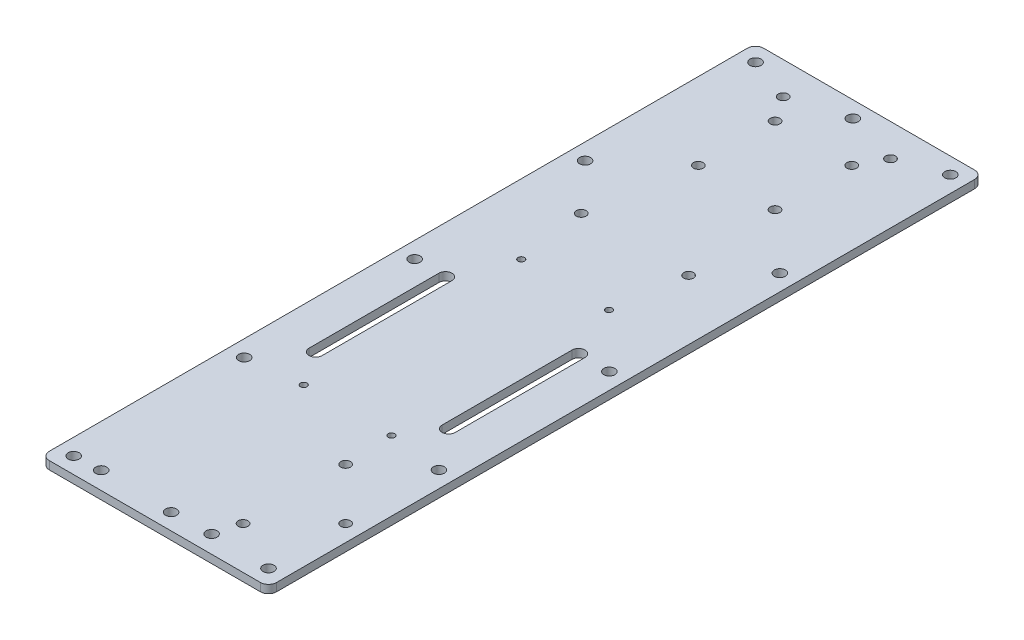
SolidWorks part; units mm, degrees
ref_plane "Front Plane" through (0, 0, 0) normal (0, 0, 1) x (1, 0, 0)
ref_plane "Top Plane" through (0, 0, 0) normal (0, 1, 0) x (1, 0, 0)
ref_plane "Right Plane" through (0, 0, 0) normal (1, 0, 0) x (0, 0, -1)
sketch "Sketch2" plane through (0, 0, 0) normal (0, 1, 0) x (1, 0, 0)
  line L0 (-44.45, 0) -> (44.45, 0) construction
  line L1 (-41.275, 139.7) -> (41.275, 139.7)
  line L2 (-44.45, 136.525) -> (-44.45, -136.525)
  line L3 (-41.275, -139.7) -> (41.275, -139.7)
  line L4 (44.45, 136.525) -> (44.45, -136.525)
  line L5 (0, 139.7) -> (0, -139.7) construction
  arc A0 (-44.45, -136.525) -> (-41.275, -139.7) centre (-41.275, -136.525) ccw
  arc A1 (41.275, -139.7) -> (44.45, -136.525) centre (41.275, -136.525) ccw
  arc A2 (41.275, 139.7) -> (44.45, 136.525) centre (41.275, 136.525) cw
  arc A3 (-41.275, 139.7) -> (-44.45, 136.525) centre (-41.275, 136.525) ccw
  point P8 (0, 0)
  point P13 (-44.45, -139.7)
  point P16 (44.45, -139.7)
  point P21 (-44.45, 139.7)
  dimension "D3" = 3.175
  dimension "D1" = 279.4
  dimension "D2" = 88.9
extrude "Plate Thickness" add sketch "Sketch2" along normal blind 3.175 contours L2 A0 L3 A1 L4 A2 L1 A3
sketch "Sketch3" plane through (0, 3.175, 0) normal (0, 1, 0) x (1, 0, 0)
  line L0 (-44.45, 136.525) -> (-44.45, -136.525) construction
  line L1 (-41.275, 139.7) -> (41.275, 139.7) construction
  line L4 (0, 139.7) -> (0, -139.7) construction
  line L5 (-41.275, -139.7) -> (41.275, -139.7) construction
  circle A0 centre (-38.1, 133.35) radius 2.159
  circle A1 centre (-38.1, 66.675) radius 2.159
  circle A2 centre (-38.1, -66.675) radius 2.159
  circle A3 centre (-38.1, -133.35) radius 2.159
  circle A4 centre (38.1, -133.35) radius 2.159
  circle A5 centre (38.1, -66.675) radius 2.159
  circle A6 centre (38.1, 66.675) radius 2.159
  circle A7 centre (38.1, 133.35) radius 2.159
  circle A8 centre (0, 133.35) radius 2.159
  circle A9 centre (0, -133.35) radius 2.159
  circle A10 centre (-38.1, 0) radius 2.159
  circle A11 centre (38.1, 0) radius 2.159
  dimension "D1" = 4.318
  dimension "D4" = 4.318
  dimension "D2" = 6.35
  dimension "D3" = 6.35
  dimension "D5" = 66.675
  dimension "D6" = 6.35
  dimension "D7" = 66.675
extrude "Mounting holes" cut sketch "Sketch3" against normal through all
sketch "Sketch4" plane through (0, 3.175, 0) normal (0, 1, 0) x (1, 0, 0)
  line L0 (-21.0058, 48.0812) -> (21.0058, 48.0812) construction
  line L1 (0, 0) -> (0, 139.7) construction
  line L4 (-41.275, 139.7) -> (41.275, 139.7) construction
  circle A0 centre (-21.0058, 127.0752) radius 1.905
  circle A1 centre (-21.0058, 48.0812) radius 1.905
  circle A2 centre (21.0058, 48.0812) radius 1.905
  circle A3 centre (21.0058, 127.0752) radius 1.905
  point P13 (0, 48.0812)
  point P17 (0, 69.85)
  point P18 (0, 69.85)
  dimension "D1" = 3.81
  dimension "D2" = 78.994
  dimension "D3" = 42.0116
extrude "Jetson Holes (w/ mount)" cut sketch "Sketch4" against normal through all
sketch "Sketch5" plane through (0, 3.175, 0) normal (0, 1, 0) x (1, 0, 0)
  circle A1 centre (-14.3419, 117.2351) radius 1.905
  circle A3 centre (15.6555, 117.2351) radius 1.905
  circle A4 centre (15.6555, 87.2377) radius 1.905
  circle A5 centre (-14.3419, 87.2377) radius 1.905
  dimension "D1" = 3.81
  dimension "D2" = 29.9974
  dimension "D3" = 29.9974
extrude "PDB holes" cut sketch "Sketch5" against normal through all
sketch "Sketch6" plane through (0, 3.175, 0) normal (0, 1, 0) x (1, 0, 0)
  circle A6 centre (38.0032, -103.0828) radius 1.905
  circle A7 centre (17.9372, -83.0168) radius 1.905
  circle A8 centre (17.9372, -123.1488) radius 1.905
  dimension "D5" = 3.81
  dimension "D6" = 40.132
  dimension "D7" = 20.066
  dimension "D8" = 20.066
extrude "Lidar Holes" cut sketch "Sketch6" against normal through all
sketch "Sketch7" plane through (0, 3.175, 0) normal (0, 1, 0) x (1, 0, 0)
  line L0 (0, 139.7) -> (0, -139.7) construction
  line L1 (-41.275, 139.7) -> (41.275, 139.7) construction
  line L2 (-41.275, -139.7) -> (41.275, -139.7) construction
  line L3 (17.145, 20.7699) -> (-17.145, 20.7699) construction
  circle A0 centre (-17.145, 20.7699) radius 1.27
  circle A1 centre (-17.145, -64.3201) radius 1.27
  circle A2 centre (17.145, -64.3201) radius 1.27
  circle A3 centre (17.145, 20.7699) radius 1.27
  point P14 (0, 20.7699)
  dimension "D1" = 2.54
  dimension "D2" = 85.09
  dimension "D3" = 34.29
extrude "PixHawk Holes" cut sketch "Sketch7" against normal through all
sketch "Sketch8" plane through (0, 3.175, 0) normal (0, 1, 0) x (1, 0, 0)
  line L0 (0, 139.7) -> (0, -115.5095) construction
  line L1 (-41.275, 139.7) -> (41.275, 139.7) construction
  line L2 (-26.035, -0.006) -> (-26.035, -50.806) construction
  line L3 (-23.495, -0.006) -> (-23.495, -50.806)
  line L4 (-28.575, -0.006) -> (-28.575, -50.806)
  line L5 (26.035, -0.006) -> (26.035, -50.806) construction
  line L6 (23.495, -0.006) -> (23.495, -50.806)
  line L7 (28.575, -0.006) -> (28.575, -50.806)
  arc A0 (-23.495, -0.006) -> (-28.575, -0.006) centre (-26.035, -0.006) ccw
  arc A1 (-28.575, -50.806) -> (-23.495, -50.806) centre (-26.035, -50.806) ccw
  arc A2 (23.495, -0.006) -> (28.575, -0.006) centre (26.035, -0.006) cw
  arc A3 (28.575, -50.806) -> (23.495, -50.806) centre (26.035, -50.806) cw
  point P7 (-26.035, -25.406)
  point P14 (26.035, -25.406)
  dimension "D1" = 50.8
  dimension "D2" = 5.08
  dimension "D3" = 26.035
extrude "Battery Holes" cut sketch "Sketch8" against normal through all
sketch "Sketch9" plane through (0, 3.175, 0) normal (0, 1, 0) x (1, 0, 0)
  circle A0 centre (-27.8687, -132.8308) radius 2.159
  circle A1 centre (15.3113, -132.8308) radius 2.159
  point P4 (-28.5935, -133.4651)
  dimension "D1" = 4.318
  dimension "D2" = 4.318
  dimension "D3" = 43.18
extrude "Cut-Extrude1" cut sketch "Sketch9" against normal through all
